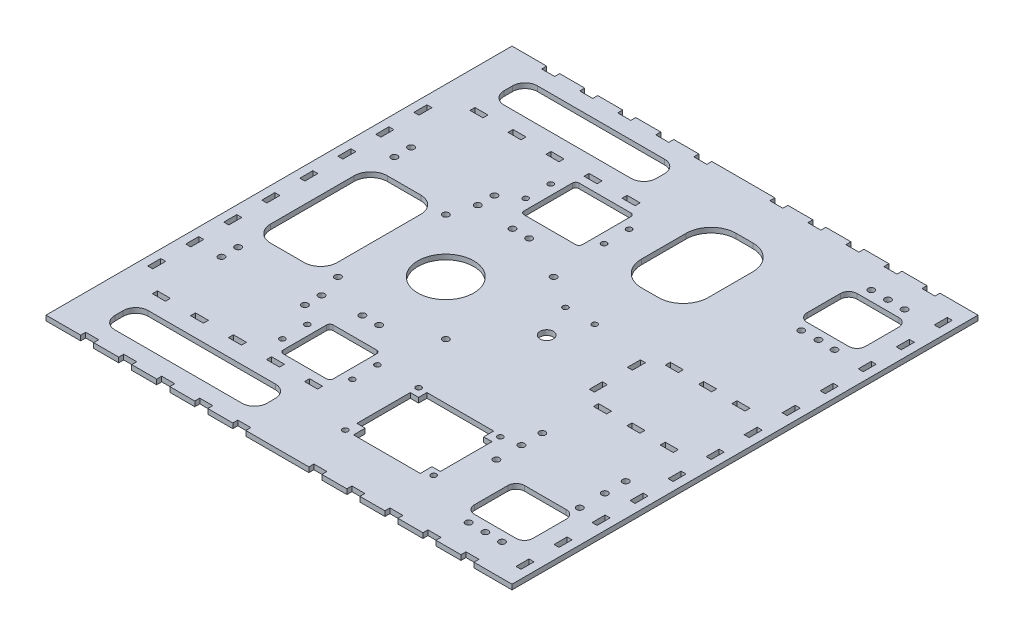
SolidWorks part; units mm, degrees
material "ENPH 253 Hardboard"
ref_plane "Front Plane" through (0, 0, 0) normal (0, 0, 1) x (1, 0, 0)
ref_plane "Top Plane" through (0, 0, 0) normal (0, 1, 0) x (1, 0, 0)
ref_plane "Right Plane" through (0, 0, 0) normal (1, 0, 0) x (0, 0, -1)
sketch "Sketch1" plane through (0, 0, 0) normal (0, 1, 0) x (1, 0, 0)
  line L0 (0, -139.7) -> (0, 139.7) construction
  line L1 (-139.7, 139.7) -> (139.7, 139.7)
  line L2 (-139.7, 139.7) -> (-139.7, -139.7)
  line L3 (-139.7, -139.7) -> (139.7, -139.7)
  line L4 (139.7, 139.7) -> (139.7, -139.7)
  line L5 (-139.7, 139.7) -> (139.7, -139.7) construction
  line L6 (-139.7, -139.7) -> (139.7, 139.7) construction
  line L12 (-139.7, 0) -> (139.7, 0) construction
  point P0 (0, 0)
  dimension "D1" = 279.4
  dimension "D2" = 279.4
extrude "Boss-Extrude1" add sketch "Sketch1" along normal blind 3
sketch "Sketch3" plane through (0, 0, 0) normal (0, -1, 0) x (-1, 0, 0)
  line L0 (-139.7, -139.7) -> (-139.7, 139.7) construction
  line L1 (-134.7, 129.3) -> (-131.7, 129.3)
  line L2 (-134.7, 129.3) -> (-134.7, 121.5)
  line L3 (-134.7, 121.5) -> (-131.7, 121.5)
  line L4 (-131.7, 129.3) -> (-131.7, 121.5)
  line L5 (-139.7, 139.7) -> (139.7, 139.7) construction
  dimension "D1" = 5
  dimension "D2" = 10.4
  dimension "D3" = 7.8
  dimension "D4" = 3
extrude "Cut-Extrude2" cut sketch "Sketch3" against normal through all
pattern_linear "LPattern1" count 12 spacing 22.8 along (0, 0, 1) of "Cut-Extrude2"
sketch "Sketch5" plane through (0, 0, 0) normal (0, -1, 0) x (1, 0, 0)
  line L0 (139.7, -139.7) -> (-139.7, -139.7) construction
  line L1 (109.1, -139.7) -> (116.9, -139.7)
  line L2 (109.1, -139.7) -> (109.1, -136.7)
  line L3 (109.1, -136.7) -> (116.9, -136.7)
  line L4 (116.9, -139.7) -> (116.9, -136.7)
  line L5 (139.7, 139.7) -> (139.7, -139.7) construction
  dimension "D1" = 22.8
  dimension "D2" = 7.8
  dimension "D3" = 3
extrude "Cut-Extrude3" cut sketch "Sketch5" against normal through all
pattern_linear "LPattern2" count 11 spacing 22.8 along (-1, 0, 0) skipping (5, 0) of "Cut-Extrude3"
mirror "Mirror2" about plane through (0, 0, 0) normal (0, 0, 1) of "LPattern2"
sketch "Sketch6" plane through (0, 0, 0) normal (0, -1, 0) x (1, 0, 0)
  line L0 (63.5, -139.7) -> (48.5, -139.7) construction
  line L1 (-134.7, -83.7) -> (-131.7, -83.7)
  line L2 (-134.7, -83.7) -> (-134.7, -75.9)
  line L3 (-134.7, -75.9) -> (-131.7, -75.9)
  line L4 (-131.7, -83.7) -> (-131.7, -75.9)
  line L5 (-139.7, -139.7) -> (-139.7, 139.7) construction
  dimension "D1" = 56
  dimension "D2" = 5
  dimension "D3" = 3
  dimension "D4" = 7.8
extrude "Cut-Extrude4" cut sketch "Sketch6" against normal through all
pattern_linear "LPattern3" count 8 spacing 22.8 along (0, 0, 1) of "Cut-Extrude4"
sketch "Sketch7" plane through (0, 0, 0) normal (0, -1, 0) x (-1, 0, 0)
  line L1 (139.7, 139.7) -> (139.7, -139.7) construction
  line L3 (-63.5, 139.7) -> (-48.5, 139.7) construction
  circle A0 centre (39.7, 0) radius 16.75
  dimension "D1" = 33.5
  dimension "D2" = 100
  dimension "D3" = 139.7
extrude "Cut-Extrude5" cut sketch "Sketch7" against normal through all
hole_wizard "#6 Clearance Hole1" positions "Sketch8" profile "Sketch9" hole size "#6" standard "ANSI Inch" end condition through all
sketch "Sketch8" plane through (0, 3, 0) normal (0, 1, 0) x (1, 0, 0)
  line L0 (-72.025, -32.325) -> (-72.025, 32.325) construction
  line L1 (-72.025, 32.325) -> (-7.375, 32.325) construction
  line L2 (-7.375, 32.325) -> (-7.375, -32.325) construction
  line L3 (-7.375, -32.325) -> (-72.025, -32.325) construction
  point P0 (-72.025, -32.325)
  point P2 (-72.025, 32.325)
  point P4 (-7.375, 32.325)
  point P6 (-7.375, -32.325)
  dimension "D1" = 64.65
  dimension "D2" = 64.65
  dimension "D3" = 90
  dimension "D4" = 64.65
  dimension "D5" = 32.325
  dimension "D6" = 32.325
sketch "Sketch9" plane through (-72.025, 3, 32.325) normal (1, 0, 0) x (0, 0, 1)
  line L0 (0, 0) -> (0, 3)
  line L1 (0, 3) -> (1.8986, 3)
  line L2 (1.8986, 3) -> (1.8986, 0)
  line L5 (1.8986, 0) -> (0, 0)
  line L11 (0, -6.35) -> (0, 107.95) construction
  dimension "Thru Hole Dia." = 3.7973
  dimension "Thru Hole Depth" = 3
hole_wizard "#6 Clearance Hole2" positions "Sketch10" profile "Sketch11" hole size "#6" standard "ANSI Inch" end condition through all
sketch "Sketch10" plane through (0, 3, 0) normal (0, 1, 0) x (1, 0, 0)
  line L1 (-118.9, 139.7) -> (-139.7, 139.7) construction
  line L2 (-139.7, -139.7) -> (-118.9, -139.7) construction
  line L3 (-73.3, 139.7) -> (-88.3, 139.7) construction
  line L4 (-88.3, -139.7) -> (-73.3, -139.7) construction
  line L5 (-139.7, 139.7) -> (-139.7, -139.7) construction
  point P0 (-117.36, 56.83)
  point P2 (-67.36, 56.83)
  point P4 (-117.36, -56.83)
  point P6 (-67.36, -56.83)
  point P22 (-67.36, -46.83)
  point P24 (-117.36, -46.83)
  point P26 (-67.36, 46.83)
  point P28 (-117.36, 46.83)
  dimension "D2" = 50
  dimension "D3" = 22.34
  dimension "D4" = 50
  dimension "D5" = 82.87
  dimension "D6" = 82.87
  dimension "D7" = 82.87
  dimension "D8" = 82.87
  dimension "D9" = 10
  dimension "D10" = 10
  dimension "D11" = 50
  dimension "D12" = 10
  dimension "D13" = 10
  dimension "D14" = 50
  dimension "D15" = 22.34
  dimension "D16" = 22.34
  dimension "D17" = 22.34
sketch "Sketch11" plane through (-117.36, 3, -56.83) normal (1, 0, 0) x (0, 0, 1)
  line L0 (0, 0) -> (0, 3)
  line L1 (0, 3) -> (1.8986, 3)
  line L2 (1.8986, 3) -> (1.8986, 0)
  line L5 (1.8986, 0) -> (0, 0)
  line L11 (0, -6.35) -> (0, 107.95) construction
  dimension "Thru Hole Dia." = 3.7973
  dimension "Thru Hole Depth" = 3
sketch "Sketch14" plane through (0, 0, 0) normal (0, -1, 0) x (-1, 0, 0)
  line L0 (139.7, 139.7) -> (139.7, -139.7) construction
  line L1 (-17.9, 139.7) -> (19.9, 139.7) construction
  circle A0 centre (-20.8, 0) radius 4
  point P6 (-12.05, 20)
  point P7 (-29.55, 20)
  dimension "D1" = 8
  dimension "D2" = 160.5
  dimension "D3" = 139.7
  dimension "D4" = 8.75
  dimension "D5" = 20
  dimension "D6" = 8.75
extrude "Cut-Extrude6" cut sketch "Sketch14" against normal through all
sketch "Sketch16" plane through (0, 0, 0) normal (0, -1, 0) x (1, 0, 0)
  line L0 (-139.7, -139.7) -> (-139.7, 139.7) construction
  line L1 (-118.9, 96.7) -> (-111.1, 96.7)
  line L2 (-118.9, 96.7) -> (-118.9, 93.7)
  line L3 (-118.9, 93.7) -> (-111.1, 93.7)
  line L4 (-111.1, 96.7) -> (-111.1, 93.7)
  line L7 (-111.1, 136.7) -> (-118.9, 136.7) construction
  dimension "D1" = 20.8
  dimension "D2" = 7.8
  dimension "D3" = 40
  dimension "D4" = 3
extrude "Cut-Extrude8" cut sketch "Sketch16" against normal through all
pattern_linear "LPattern5" count 5 spacing 22.8 along (1, 0, 0) of "Cut-Extrude8"
mirror "Mirror4" about plane through (0, 0, 0) normal (0, 0, 1) of "LPattern5"
sketch "Sketch17" plane through (0, 0, 0) normal (0, -1, 0) x (1, 0, 0)
  line L1 (119.7, 23) -> (111.9, 23)
  line L2 (119.7, 23) -> (119.7, 20)
  line L3 (119.7, 20) -> (111.9, 20)
  line L4 (111.9, 23) -> (111.9, 20)
  line L5 (94.1, 139.7) -> (109.1, 139.7) construction
  line L6 (139.7, 139.7) -> (139.7, -139.7) construction
  point P8 (119.7, 21.5)
  dimension "D1" = 116.7
  dimension "D2" = 20
  dimension "D3" = 7.8
  dimension "D4" = 3
extrude "Cut-Extrude9" cut sketch "Sketch17" against normal through all
pattern_linear "LPattern6" count 3 spacing 20 along (-1, 0, 0) of "Cut-Extrude9"
sketch "Sketch18" plane through (0, 0, 0) normal (0, -1, 0) x (-1, 0, 0)
  line L0 (-139.7, -139.7) -> (-139.7, 139.7) construction
  line L1 (-64.7, -15.3) -> (-61.7, -15.3)
  line L2 (-64.7, -15.3) -> (-64.7, -7.5)
  line L3 (-64.7, -7.5) -> (-61.7, -7.5)
  line L4 (-61.7, -15.3) -> (-61.7, -7.5)
  line L5 (-71.3, -139.7) -> (-86.3, -139.7) construction
  dimension "D1" = 7.8
  dimension "D2" = 3
  dimension "D3" = 75
  dimension "D4" = 124.4
extrude "Cut-Extrude10" cut sketch "Sketch18" against normal through all
mirror "Mirror5" about plane through (0, 0, 0) normal (0, 0, 1) of "Cut-Extrude10", "LPattern6", "Cut-Extrude9"
sketch "Sketch19" plane through (0, 0, 0) normal (0, -1, 0) x (1, 0, 0)
  line L0 (0, 0) -> (139.7, 0) construction
  line L1 (24.7, -109.7) -> (34.7, -109.7)
  line L2 (9.7, -94.7) -> (9.7, -68)
  line L3 (24.7, -53) -> (34.7, -53)
  line L4 (49.7, -94.7) -> (49.7, -68)
  line L9 (139.7, 139.7) -> (139.7, -139.7) construction
  line L10 (86.3, -139.7) -> (71.3, -139.7) construction
  line L11 (79.7, -23) -> (71.9, -23) construction
  line L16 (-139.7, -139.7) -> (-139.7, 139.7) construction
  line L17 (-89.7, 35) -> (-109.7, 35)
  line L18 (-79.7, 25) -> (-79.7, -25)
  line L19 (-89.7, -35) -> (-109.7, -35)
  line L20 (-119.7, 25) -> (-119.7, -25)
  line L21 (9.7, 102.7) -> (59.7, 102.7) construction
  line L22 (9.7, 65.7) -> (59.7, 65.7) construction
  line L23 (9.7, 65.7) -> (9.7, 109.7) construction
  line L24 (9.7, 109.7) -> (59.7, 109.7) construction
  line L25 (59.7, 65.7) -> (59.7, 109.7) construction
  line L29 (14.7, 65.7) -> (54.7, 65.7)
  line L30 (25.7, 139.7) -> (40.7, 139.7) construction
  line L32 (59.7, 102.7) -> (59.7, 71.7) construction
  line L34 (9.7, 102.7) -> (9.7, 70.7) construction
  line L35 (139.7, 139.7) -> (139.7, -139.7) construction
  line L38 (9.7, 102.7) -> (9.7, 70.7)
  line L39 (9.7, 70.7) -> (14.7, 70.7)
  line L40 (14.7, 70.7) -> (14.7, 65.7)
  line L41 (54.7, 65.7) -> (54.7, 71.7)
  line L42 (54.7, 71.7) -> (59.7, 71.7)
  line L43 (59.7, 71.7) -> (59.7, 102.7)
  line L45 (14.7, 102.7) -> (54.7, 102.7) construction
  line L46 (14.7, 102.7) -> (14.7, 109.7)
  line L47 (14.7, 109.7) -> (54.7, 109.7)
  line L48 (54.7, 102.7) -> (54.7, 109.7)
  line L49 (9.7, 102.7) -> (14.7, 102.7)
  line L50 (54.7, 102.7) -> (59.7, 102.7)
  arc A1 (34.7, -53) -> (49.7, -68) centre (34.7, -68) cw
  arc A2 (34.7, -109.7) -> (49.7, -94.7) centre (34.7, -94.7) ccw
  arc A3 (24.7, -109.7) -> (9.7, -94.7) centre (24.7, -94.7) cw
  arc A4 (9.7, -68) -> (24.7, -53) centre (24.7, -68) cw
  circle A9 centre (-39.7, 0) radius 16.75 construction
  arc A10 (-79.7, -25) -> (-89.7, -35) centre (-89.7, -25) cw
  arc A11 (-89.7, 35) -> (-79.7, 25) centre (-89.7, 25) cw
  arc A12 (-109.7, 35) -> (-119.7, 25) centre (-109.7, 25) ccw
  arc A13 (-109.7, -35) -> (-119.7, -25) centre (-109.7, -25) cw
  point P43 (-79.7, -35)
  point P46 (-79.7, 35)
  dimension "D9" = 35
  dimension "D10" = 10
  dimension "D11" = 44
  dimension "D12" = 50
  dimension "D1" = 15
  dimension "D2" = 30
  dimension "D3" = 90
  dimension "D4" = 30
  dimension "D5" = 40
  dimension "D6" = 70
  dimension "D7" = 20
  dimension "D8" = 40
  dimension "D13" = 5
  dimension "D15" = 7
  dimension "D17" = 30
  dimension "D18" = 80
  dimension "D14" = 6
extrude "Cut-Extrude11" cut sketch "Sketch19" against normal through all
hole_wizard "#4 Clearance Hole1" positions "Sketch20" profile "Sketch21" hole size "#4" standard "ANSI Inch" end condition through all
sketch "Sketch20" plane through (0, 3, 0) normal (0, 1, 0) x (1, 0, 0)
  line L0 (9.7, -102.7) -> (9.7, -70.7) construction
  line L1 (59.7, -71.7) -> (59.7, -102.7) construction
  line L2 (59.7, -102.7) -> (54.7, -102.7) construction
  line L3 (14.7, -102.7) -> (9.7, -102.7) construction
  point P0 (9.7, -65.7)
  point P2 (59.7, -66.7)
  point P4 (59.7, -106.7)
  point P6 (9.7, -109.7)
  dimension "D1" = 5
  dimension "D2" = 7
  dimension "D3" = 4
  dimension "D4" = 1
sketch "Sketch21" plane through (9.7, 3, 65.7) normal (1, 0, 0) x (0, 0, 1)
  line L0 (0, 0) -> (0, 3)
  line L1 (0, 3) -> (1.6319, 3)
  line L2 (1.6319, 3) -> (1.6319, 0)
  line L5 (1.6319, 0) -> (0, 0)
  line L11 (0, -6.35) -> (0, 107.95) construction
  dimension "Thru Hole Dia." = 3.2639
  dimension "Thru Hole Depth" = 3
sketch "Sketch22" plane through (0, 3, 0) normal (0, 1, 0) x (1, 0, 0)
  line L5 (92.2, -84.7) -> (117.2, -84.7)
  line L6 (87.2, -89.7) -> (87.2, -109.7)
  line L7 (92.2, -114.7) -> (117.2, -114.7)
  line L8 (122.2, -89.7) -> (122.2, -109.7)
  line L9 (139.7, -139.7) -> (139.7, 139.7) construction
  line L10 (94.1, -139.7) -> (109.1, -139.7) construction
  line L11 (139.7, 0) -> (94.1968, 0) construction
  line L12 (92.2, 114.7) -> (117.2, 114.7)
  line L13 (122.2, 89.7) -> (122.2, 109.7)
  line L14 (92.2, 84.7) -> (117.2, 84.7)
  line L15 (87.2, 89.7) -> (87.2, 109.7)
  arc A0 (87.2, -109.7) -> (92.2, -114.7) centre (92.2, -109.7) ccw
  arc A1 (92.2, -84.7) -> (87.2, -89.7) centre (92.2, -89.7) ccw
  arc A2 (117.2, -84.7) -> (122.2, -89.7) centre (117.2, -89.7) cw
  arc A3 (117.2, -114.7) -> (122.2, -109.7) centre (117.2, -109.7) ccw
  arc A4 (92.2, 84.7) -> (87.2, 89.7) centre (92.2, 89.7) cw
  arc A5 (122.2, 89.7) -> (117.2, 84.7) centre (117.2, 89.7) cw
  arc A6 (117.2, 114.7) -> (122.2, 109.7) centre (117.2, 109.7) cw
  arc A7 (92.2, 114.7) -> (87.2, 109.7) centre (92.2, 109.7) ccw
  point P2 (87.2, -114.7)
  point P9 (87.2, -84.7)
  point P23 (122.2, -84.7)
  point P26 (122.2, -114.7)
  point P29 (87.2, 84.7)
  point P32 (122.2, 84.7)
  point P35 (122.2, 114.7)
  point P38 (87.2, 114.7)
  dimension "D1" = 5
  dimension "D5" = 17.5
  dimension "D6" = 35
  dimension "D7" = 25
  dimension "D8" = 30
extrude "Cut-Extrude12" cut sketch "Sketch22" against normal up to next contours L8 L5 L6 L7 | L15 L14 L13 L12 region at (104.7, 3, 99.7) region at (104.7, 3, -99.7)
hole_wizard "#6 Clearance Hole3" positions "Sketch25" profile "Sketch26" hole size "#6" standard "ANSI Inch" end condition through all
sketch "Sketch25" plane through (0, 3, 0) normal (0, 1, 0) x (1, 0, 0)
  line L0 (70.35, -52.2) -> (70.35, -79.7) construction
  line L2 (70.35, -79.7) -> (120.35, -79.7) construction
  line L3 (120.35, -79.7) -> (120.35, -52.2) construction
  line L4 (120.35, -52.2) -> (70.35, -52.2) construction
  line L6 (70.35, -64.7) -> (120.35, -64.7) construction
  line L8 (92.2, -84.7) -> (117.2, -84.7) construction
  line L9 (104.7, 79.0309) -> (104.7, 120.7) construction
  line L10 (104.7, 120.7) -> (94.7, 120.7) construction
  line L11 (94.7, 120.7) -> (94.7, 78.7) construction
  line L12 (94.7, 78.7) -> (114.7, 78.7) construction
  line L13 (114.7, 78.7) -> (114.7, 120.7) construction
  line L14 (114.7, 120.7) -> (94.7, 120.7) construction
  line L16 (92.2, 84.7) -> (117.2, 84.7) construction
  line L17 (92.2, 114.7) -> (117.2, 114.7) construction
  line L18 (0, 0) -> (139.7, 0) construction
  line L19 (139.7, -139.7) -> (139.7, 139.7) construction
  point P0 (94.7, 120.7)
  point P2 (114.7, 120.7)
  point P4 (114.7, 78.7)
  point P6 (94.7, 78.7)
  point P8 (104.7, 79.0309)
  point P10 (104.7, 120.7)
  point P12 (70.35, -52.2)
  point P14 (70.35, -79.7)
  point P16 (70.35, -64.7)
  point P18 (120.35, -64.7)
  point P20 (120.35, -52.2)
  point P22 (120.35, -79.7)
  point P43 (104.7, -84.7)
  point P56 (104.7, 84.7)
  point P59 (161.7487, 56.9763)
  point P68 (114.7, -120.7)
  point P69 (104.7, -120.7)
  point P70 (94.7, -120.7)
  point P71 (-44.7, 45)
  point P73 (-34.7, 45)
  point P75 (-44.7, -45)
  point P77 (-34.7, -45)
  dimension "D1" = 27.5
  dimension "D2" = 5
  dimension "D3" = 15
  dimension "D4" = 50
  dimension "D5" = 15.65
  dimension "D6" = 20
  dimension "D7" = 10
  dimension "D8" = 6
  dimension "D9" = 6
  dimension "D10" = 90
  dimension "D11" = 45
  dimension "D12" = 10
  dimension "D13" = 34.7
sketch "Sketch26" plane through (94.7, 3, -120.7) normal (1, 0, 0) x (0, 0, 1)
  line L0 (0, 0) -> (0, 3)
  line L1 (0, 3) -> (1.8986, 3)
  line L2 (1.8986, 3) -> (1.8986, 0)
  line L5 (1.8986, 0) -> (0, 0)
  line L11 (0, -6.35) -> (0, 107.95) construction
  dimension "Thru Hole Dia." = 3.7973
  dimension "Thru Hole Depth" = 3
hole_wizard "#4 Clearance Hole2" positions "Sketch27" profile "Sketch28" hole size "#4" standard "ANSI Inch" end condition up to next
sketch "Sketch27" plane through (0, 3, 0) normal (0, 1, 0) x (1, 0, 0)
  point P0 (12.05, 20)
  point P2 (29.55, 20)
sketch "Sketch28" plane through (12.05, 3, -20) normal (1, 0, 0) x (0, 0, 1)
  line L0 (0, 0) -> (0, 3)
  line L1 (0, 3) -> (1.6319, 3)
  line L2 (1.6319, 3) -> (1.6319, 0)
  line L5 (1.6319, 0) -> (0, 0)
  line L11 (0, -6.35) -> (0, 107.95) construction
  dimension "Thru Hole Dia." = 3.2639
  dimension "Thru Hole Depth" = 3
sketch "Sketch29" plane through (0, 3, 0) normal (0, 1, 0) x (1, 0, 0)
  line L0 (-50.5, -86.7) -> (-50.5, -60.7)
  line L1 (-17.5, 88.7) -> (-48.5, 88.7)
  line L2 (-15.5, 86.7) -> (-15.5, 57.7)
  line L3 (-17.5, 55.7) -> (-48.5, 55.7)
  line L4 (-50.5, 86.7) -> (-50.5, 57.7)
  line L5 (-50.5, -96.7) -> (-50.5, -93.7) construction
  line L6 (-50.5, 93.7) -> (-42.7, 93.7) construction
  line L7 (-50.5, 96.7) -> (-50.5, 93.7) construction
  line L9 (-48.5, -88.7) -> (-22.5, -88.7)
  line L12 (-20.5, -86.7) -> (-20.5, -74.2636)
  line L15 (-48.5, -58.7) -> (-22.5, -58.7)
  line L16 (-20.5, -74.2636) -> (-20.5, -60.7)
  line L17 (-27.7, -93.7) -> (-19.9, -93.7) construction
  arc A0 (-15.5, 57.7) -> (-17.5, 55.7) centre (-17.5, 57.7) cw
  arc A1 (-17.5, 88.7) -> (-15.5, 86.7) centre (-17.5, 86.7) cw
  arc A2 (-48.5, 88.7) -> (-50.5, 86.7) centre (-48.5, 86.7) ccw
  arc A3 (-48.5, 55.7) -> (-50.5, 57.7) centre (-48.5, 57.7) cw
  arc A4 (-22.5, -88.7) -> (-20.5, -86.7) centre (-22.5, -86.7) ccw
  arc A5 (-22.5, -58.7) -> (-20.5, -60.7) centre (-22.5, -60.7) cw
  arc A6 (-50.5, -60.7) -> (-48.5, -58.7) centre (-48.5, -60.7) cw
  arc A7 (-48.5, -88.7) -> (-50.5, -86.7) centre (-48.5, -86.7) cw
  point P8 (-15.5, 88.7)
  point P11 (-50.5, 88.7)
  point P14 (-50.5, 55.7)
  point P27 (-50.5, -88.7)
  point P31 (-23.8, -93.7)
  point P34 (-20.5, -88.7)
  point P39 (-50.5, -58.7)
  point P40 (-48.5, -60.7)
  dimension "D3" = 2
  dimension "D9" = 2
  dimension "D5" = 2
  dimension "D1" = 35
  dimension "D2" = 33
  dimension "D4" = 5
  dimension "D6" = 30
  dimension "D7" = 5
  dimension "D8" = 30
extrude "Cut-Extrude13" cut sketch "Sketch29" against normal up to next
sketch "Sketch30" plane through (0, 3, 0) normal (0, 1, 0) x (1, 0, 0)
  line L0 (-22.5, -58.7) -> (-48.5, -58.7) construction
  line L1 (-50.5, -60.7) -> (-50.5, -86.7) construction
  line L2 (-20.5, -86.7) -> (-20.5, -60.7) construction
  line L3 (-50.5, 86.7) -> (-50.5, 57.7) construction
  line L4 (-56.5, 64.7) -> (-9.5, 64.7) construction
  line L5 (-56.5, 64.7) -> (-56.5, 79.7) construction
  line L6 (-56.5, 79.7) -> (-9.5, 79.7) construction
  line L7 (-9.5, 64.7) -> (-9.5, 79.7) construction
  line L8 (-15.5, 57.7) -> (-15.5, 86.7) construction
  line L9 (-48.5, 55.7) -> (-17.5, 55.7) construction
  point P0 (-56.5, -81.2)
  point P1 (-56.5, -66.2)
  point P2 (-14.5, -66.2)
  point P3 (-14.5, -81.2)
  point P20 (0, 0)
  dimension "D1" = 15
  dimension "D2" = 15
  dimension "D3" = 7.5
  dimension "D4" = 7.5
  dimension "D5" = 6
  dimension "D6" = 6
  dimension "D7" = 15
  dimension "D8" = 6
  dimension "D9" = 6
  dimension "D10" = 9
hole_wizard "#4 Clearance Hole3" positions "Sketch31" profile "Sketch32" hole size "#4" standard "ANSI Inch" end condition through all
sketch "Sketch31" plane through (0, 3, 0) normal (0, 1, 0) x (1, 0, 0)
  point P0 (-56.5, 64.7)
  point P3 (-56.5, 79.7)
  point P6 (-9.5, 79.7)
  point P9 (-9.5, 64.7)
  point P12 (-56.5, -66.2)
  point P14 (-14.5, -66.2)
  point P16 (-14.5, -81.2)
  point P18 (-56.5, -81.2)
  point P22 (0, 0)
  point P23 (-56.5, -75.9831)
  point P24 (-56.5, -81.2)
  point P26 (-14.5, -81.2)
  point P28 (-14.5, -66.5277)
  point P29 (-10.0983, -70.1611)
  point P30 (-14.5, -66.2)
sketch "Sketch32" plane through (-56.5, 3, -64.7) normal (1, 0, 0) x (0, 0, 1)
  line L0 (0, 0) -> (0, 3)
  line L1 (0, 3) -> (1.6319, 3)
  line L2 (1.6319, 3) -> (1.6319, 0)
  line L5 (1.6319, 0) -> (0, 0)
  line L11 (0, -6.35) -> (0, 107.95) construction
  dimension "Thru Hole Dia." = 3.2639
  dimension "Thru Hole Depth" = 3
sketch "Sketch33" plane through (0, 3, 0) normal (0, 1, 0) x (1, 0, 0)
  line L0 (-88.3, -96.7) -> (-96.1, -96.7) construction
  line L1 (-111.4, -126.7) -> (-35.2, -126.7)
  line L2 (-118.9, -119.2) -> (-118.9, -114.2)
  line L3 (-111.4, -106.7) -> (-35.2, -106.7)
  line L4 (-27.7, -119.2) -> (-27.7, -114.2)
  line L5 (-111.4, 106.7) -> (-35.2, 106.7)
  line L6 (-118.9, 114.2) -> (-118.9, 119.2)
  line L7 (-111.4, 126.7) -> (-35.2, 126.7)
  line L8 (-27.7, 114.2) -> (-27.7, 119.2)
  line L9 (-88.3, -136.7) -> (-96.1, -136.7) construction
  line L10 (-118.9, -96.7) -> (-118.9, -93.7) construction
  line L11 (-27.7, -96.7) -> (-27.7, -93.7) construction
  line L12 (-118.9, 96.7) -> (-118.9, 93.7) construction
  line L13 (-27.7, 96.7) -> (-27.7, 93.7) construction
  line L14 (-65.5, 96.7) -> (-73.3, 96.7) construction
  line L15 (-65.5, 136.7) -> (-73.3, 136.7) construction
  arc A0 (-111.4, 106.7) -> (-118.9, 114.2) centre (-111.4, 114.2) cw
  arc A1 (-118.9, 119.2) -> (-111.4, 126.7) centre (-111.4, 119.2) cw
  arc A2 (-35.2, 126.7) -> (-27.7, 119.2) centre (-35.2, 119.2) cw
  arc A3 (-35.2, 106.7) -> (-27.7, 114.2) centre (-35.2, 114.2) ccw
  arc A4 (-35.2, -126.7) -> (-27.7, -119.2) centre (-35.2, -119.2) ccw
  arc A5 (-35.2, -106.7) -> (-27.7, -114.2) centre (-35.2, -114.2) cw
  arc A6 (-118.9, -114.2) -> (-111.4, -106.7) centre (-111.4, -114.2) cw
  arc A7 (-111.4, -126.7) -> (-118.9, -119.2) centre (-111.4, -119.2) cw
  dimension "D1" = 7.5
  dimension "D2" = 10
  dimension "D3" = 10
  dimension "D4" = 10
  dimension "D5" = 10
extrude "Cut-Extrude14" cut sketch "Sketch33" against normal up to next
equation "\"45mmm\"=50"
equation "\"D11@Sketch25\"=\"D10@Sketch25\"/2"
